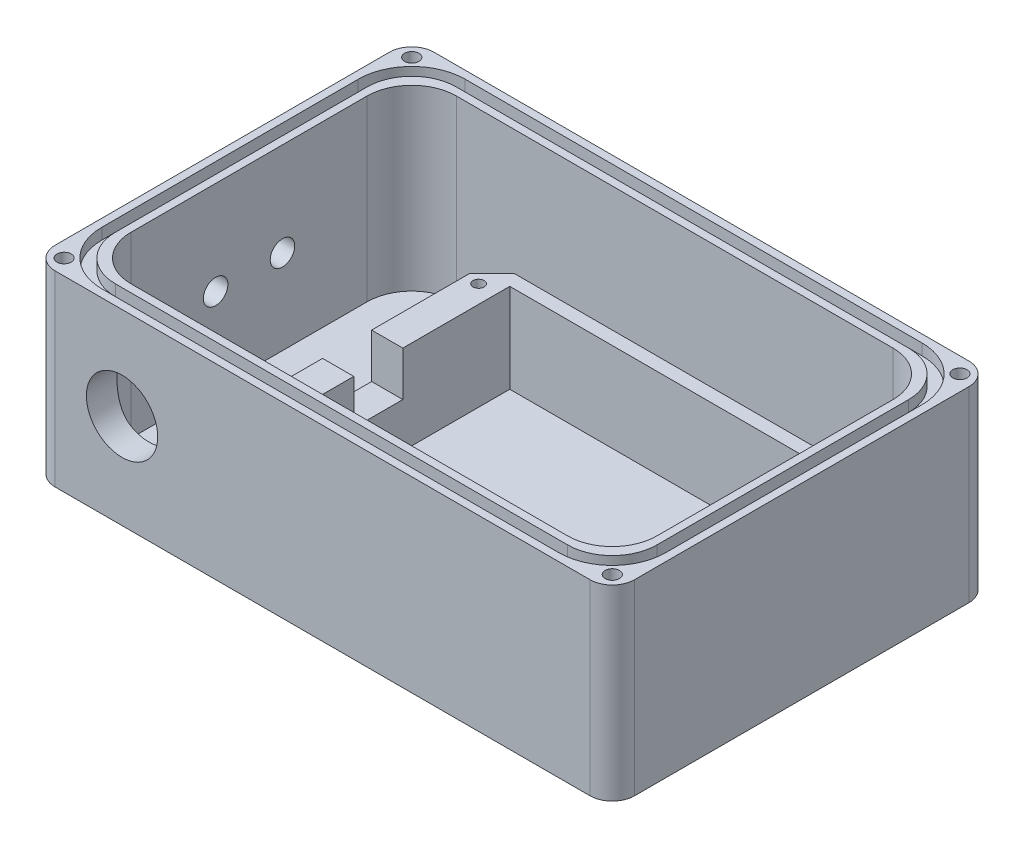
SolidWorks part; units mm, degrees
ref_plane "Front" through (0, 0, 0) normal (0, 0, 1) x (1, 0, 0)
ref_plane "Top" through (0, 0, 0) normal (0, 1, 0) x (1, 0, 0)
ref_plane "Right" through (0, 0, 0) normal (1, 0, 0) x (0, 0, -1)
sketch "Sketch1" plane through (0, 0, 0) normal (0, 1, 0) x (1, 0, 0)
  line L1 (0, 0) -> (130, 0)
  line L2 (0, 0) -> (0, 85)
  line L3 (0, 85) -> (130, 85)
  line L4 (130, 0) -> (130, 85)
  dimension "D1" = 85
  dimension "D4" = 130
extrude "Boss-Extrude1" add sketch "Sketch1" along normal blind 2
sketch "Sketch2" plane through (0, 2, 0) normal (0, 1, 0) x (1, 0, 0)
  line L1 (0, 85) -> (130, 85)
  line L2 (0, 85) -> (0, 0)
  line L3 (0, 0) -> (130, 0)
  line L4 (130, 85) -> (130, 0)
  line L5 (16, 79) -> (114, 79)
  line L6 (6, 69) -> (6, 16)
  line L7 (16, 6) -> (114, 6)
  line L8 (124, 69) -> (124, 16)
  arc A0 (114, 6) -> (124, 16) centre (114, 16) ccw
  arc A1 (114, 79) -> (124, 69) centre (114, 69) cw
  arc A2 (16, 79) -> (6, 69) centre (16, 69) ccw
  arc A3 (6, 16) -> (16, 6) centre (16, 16) ccw
  dimension "D5" = 10
  dimension "D6" = 10
  dimension "D7" = 10
  dimension "D1" = 6
  dimension "D2" = 6
  dimension "D3" = 6
  dimension "D4" = 6
extrude "Boss-Extrude2" add sketch "Sketch2" along normal blind 40
fillet "Fillet1" radius 5 1 edges at (0, 21, 0)
fillet "Fillet2" radius 5 3 edges at (0, 21, -85) (130, 21, -85) (130, 21, 0)
sketch "Sketch3" plane through (0, 42, 0) normal (0, 1, 0) x (1, 0, 0)
  line L0 (4.25, 70.75) -> (4.25, 14.25)
  line L1 (14.25, 4.25) -> (115.75, 4.25)
  line L2 (125.75, 14.25) -> (125.75, 70.75)
  line L3 (115.75, 80.75) -> (14.25, 80.75)
  line L6 (114, 79) -> (16, 79) construction
  line L7 (6, 69) -> (6, 16) construction
  line L8 (16, 6) -> (114, 6) construction
  line L9 (124, 16) -> (124, 69) construction
  line L10 (13.75, 83.25) -> (116.25, 83.25)
  line L11 (128.25, 71.25) -> (128.25, 13.75)
  line L12 (116.25, 1.75) -> (13.75, 1.75)
  line L13 (1.75, 13.75) -> (1.75, 71.25)
  arc A0 (13.75, 83.25) -> (1.75, 71.25) centre (13.75, 71.25) ccw
  arc A1 (14.25, 80.75) -> (4.25, 70.75) centre (14.25, 70.75) ccw
  arc A2 (125.75, 70.75) -> (115.75, 80.75) centre (115.75, 70.75) ccw
  arc A3 (115.75, 4.25) -> (125.75, 14.25) centre (115.75, 14.25) ccw
  arc A4 (14.25, 4.25) -> (4.25, 14.25) centre (14.25, 14.25) cw
  arc A5 (13.75, 1.75) -> (1.75, 13.75) centre (13.75, 13.75) cw
  arc A6 (128.25, 13.75) -> (116.25, 1.75) centre (116.25, 13.75) cw
  arc A7 (116.25, 83.25) -> (128.25, 71.25) centre (116.25, 71.25) cw
  point P38 (4.25, 4.25)
  dimension "D9" = 12
  dimension "D10" = 10
  dimension "D11" = 10
  dimension "D12" = 12
  dimension "D15" = 10
  dimension "D1" = 1.75
  dimension "D2" = 1.75
  dimension "D3" = 1.75
  dimension "D4" = 1.75
  dimension "D5" = 2.5
  dimension "D6" = 2.5
  dimension "D7" = 2.5
  dimension "D8" = 2.5
extrude "Cut-Extrude1" cut sketch "Sketch3" against normal blind 2.5
sketch "Sketch5" plane through (0, 2, 0) normal (0, 1, 0) x (1, 0, 0)
  line L0 (114, 79) -> (16, 79) construction
  line L1 (39, 68) -> (109, 68)
  line L2 (39, 68) -> (39, 9)
  line L3 (39, 9) -> (109, 9)
  line L4 (109, 68) -> (109, 9)
  line L5 (114, 79) -> (16, 79) construction
  line L6 (16, 6) -> (114, 6) construction
  line L7 (124, 16) -> (124, 69) construction
  line L8 (32, 66) -> (37, 71)
  line L9 (37, 71) -> (110.85, 71)
  line L10 (32, 66) -> (32, 11)
  line L11 (37, 6) -> (110.85, 6)
  line L12 (115.85, 66) -> (115.85, 11)
  line L13 (32, 11) -> (37, 6)
  line L14 (110.85, 6) -> (115.85, 11)
  line L15 (110.85, 71) -> (115.85, 66)
  circle A0 centre (35, 65) radius 1.25
  circle A1 centre (35, 12) radius 1.25
  circle A2 centre (112.9918, 13.1314) radius 1.25
  circle A3 centre (113, 61.1314) radius 1.25
  point P20 (32, 71)
  point P21 (115.85, 6)
  point P22 (32, 6)
  point P23 (115.85, 71)
  dimension "D6" = 78
  dimension "D1" = 70
  dimension "D2" = 59
  dimension "D3" = 11
  dimension "D4" = 3
  dimension "D5" = 15
  dimension "D7" = 53
  dimension "D8" = 48
  dimension "D9" = 4
  dimension "D10" = 14
  dimension "D11" = 6
  dimension "D12" = 3
  dimension "D13" = 3
  dimension "D14" = 7
  dimension "D15" = 4
  dimension "D16" = 4
  dimension "D21" = 6.85
extrude "Boss-Extrude4" add sketch "Sketch5" along normal blind 20
sketch "Sketch8" plane through (0, 0, 0) normal (0, 0, 1) x (1, 0, 0)
  line L0 (5, 42) -> (5, 0) construction
  circle A0 centre (20, 21.2548) radius 8
  dimension "D1" = 15
extrude "Cut-Extrude3" cut sketch "Sketch8" against normal up to next
sketch "Sketch9" plane through (0, 0, 0) normal (-1, 0, 0) x (0, 0, 1)
  line L0 (-80, 42) -> (-5, 42) construction
  line L1 (-80, 0) -> (-5, 0) construction
  line L2 (-80, 42) -> (-80, 0) construction
  line L3 (-5, 0) -> (-5, 42) construction
  circle A0 centre (-50, 21) radius 2.75
  circle A1 centre (-35, 21) radius 2.75
  dimension "D1" = 15
  dimension "D2" = 21
  dimension "D3" = 21
  dimension "D4" = 30
  dimension "D5" = 30
extrude "Cut-Extrude4" cut sketch "Sketch9" against normal up to next
sketch "Sketch10" plane through (0, 42, 0) normal (0, 1, 0) x (1, 0, 0)
  line L0 (125, 85) -> (5, 85) construction
  line L1 (0, 80) -> (0, 5) construction
  line L2 (5, 0) -> (125, 0) construction
  line L3 (130, 5) -> (130, 80) construction
  circle A0 centre (3.5, 81.5) radius 1.6
  circle A1 centre (3.5, 3.5) radius 1.6
  circle A2 centre (126.5, 3.5) radius 1.6
  circle A3 centre (126.5, 81.5) radius 1.6
  dimension "D1" = 3.5
  dimension "D3" = 3.5
  dimension "D5" = 3.5
  dimension "D7" = 3.5
  dimension "D2" = 3.5
  dimension "D4" = 3.5
  dimension "D6" = 3.5
  dimension "D8" = 3.5
extrude "Cut-Extrude5" cut sketch "Sketch10" against normal blind 10
sketch "Sketch11" plane through (0, 22, 0) normal (0, 1, 0) x (1, 0, 0)
  line L0 (39, 68) -> (39, 9) construction
  line L1 (32, 44) -> (39, 44)
  line L2 (32, 66) -> (32, 11) construction
  line L3 (32, 44) -> (32, 33)
  line L4 (32, 66) -> (32, 11) construction
  line L5 (32, 33) -> (39, 33)
  line L6 (39, 33) -> (39, 44)
  line L7 (110.85, 71) -> (37, 71) construction
  line L8 (16, 6) -> (114, 6) construction
  dimension "D1" = 27
  dimension "D2" = 27
extrude "Cut-Extrude6" cut sketch "Sketch11" against normal blind 10
sketch "Sketch12" plane through (0, 0, -6) normal (0, 0, -1) x (-1, 0, 0)
  line L0 (-16, 42) -> (-114, 42) construction
  circle A0 centre (-19.9524, 21) radius 11
  circle A1 centre (-19.9524, 21) radius 8.4065
  dimension "D1" = 21
extrude "Cut-Extrude7" cut sketch "Sketch12" along normal blind 2
